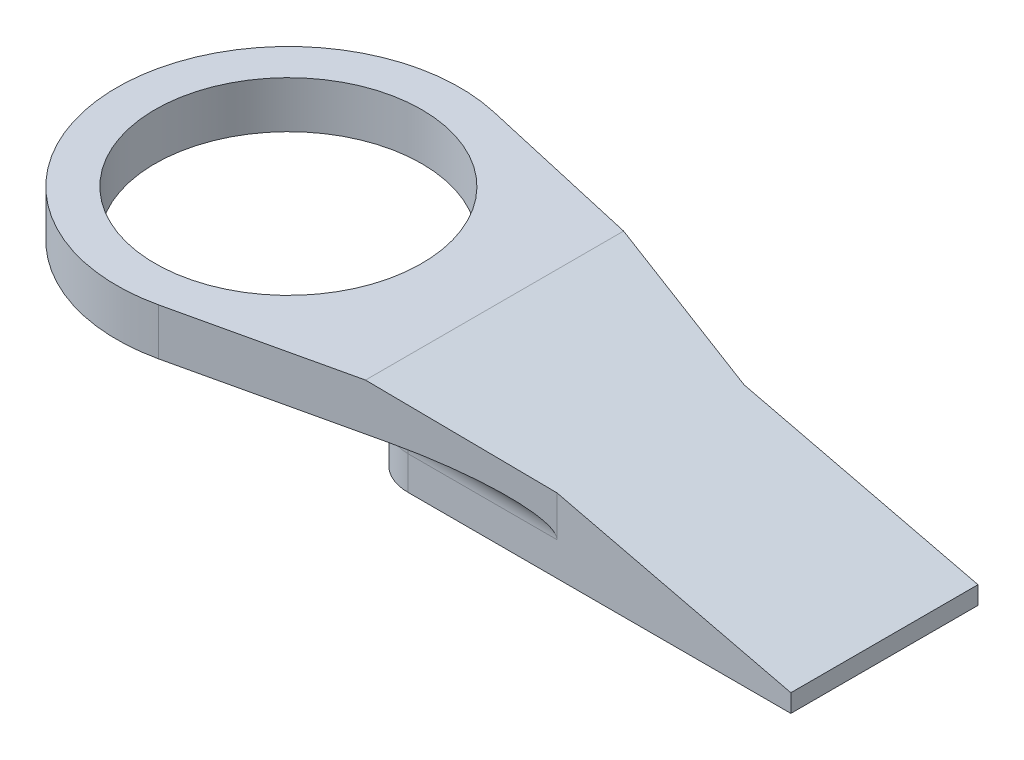
SolidWorks part; units mm, degrees
ref_plane "Front Plane" through (0, 0, 0) normal (0, 0, 1) x (1, 0, 0)
ref_plane "Top Plane" through (0, 0, 0) normal (0, 1, 0) x (1, 0, 0)
ref_plane "Right Plane" through (0, 0, 0) normal (1, 0, 0) x (0, 0, -1)
sketch "Sketch1" plane through (0, 0, 0) normal (0, 0, 1) x (1, 0, 0)
  line L0 (0, 0) -> (0, 7.15)
  line L1 (0, 7.15) -> (30, 7.15)
  line L2 (30, 7.15) -> (30, 0)
  line L3 (30, 0) -> (0, 0)
extrude "Boss-Extrude1" add sketch "Sketch1" along normal blind 12
sketch "Sketch2" plane through (0, 7.15, 0) normal (0, 1, 0) x (1, 0, 0)
  line L0 (0, -6) -> (-8.2201, -6) construction
  line L1 (0, -12) -> (0, 0) construction
  line L3 (30, 0) -> (0, 0) construction
  line L4 (15, -12) -> (-5.8205, -16.7354)
  line L5 (30, -12) -> (0, -12) construction
  line L6 (15, 0) -> (15, -12)
  line L8 (15, 0) -> (-5.7804, 4.7264)
  arc A5 (-5.7804, 4.7264) -> (-5.7405, -16.7172) centre (-8.2201, -6) ccw
  line M4 (30, 0) -> (0, 0)
  line M5 (0, 0) -> (0, -12)
  line M6 (0, -12) -> (30, -12)
extrude "Boss-Extrude2" add sketch "Sketch2" against normal blind 3 contours M6 M5 M4 region at (-7.0838, 7.15, 6)
sketch "Sketch3" plane through (0, 4.15, 0) normal (0, -1, 0) x (1, 0, 0)
  circle A1 centre (-8.2201, 6) radius 11
extrude "Cut-Extrude1" cut sketch "Sketch3" along normal blind 21
fillet "Fillet1" radius 3 2 edges at (0.9994, 2.075, 0) (0.9994, 2.075, 12)
sketch "Sketch4" plane through (0, 4.15, 0) normal (0, -1, 0) x (1, 0, 0)
  circle A1 centre (-8.2201, 6) radius 8.55
extrude "Cut-Extrude2" cut sketch "Sketch4" against normal blind 10
chamfer "Chamfer1" distance 6 distance2 25 1 edges at (30, 7.15, 6) first distance on face at (30, 3.575, 6)
sketch "Sketch5" plane through (0, 0, 0) normal (0, -1, 0) x (-1, 0, 0)
  line L0 (-2.4547, -9) -> (-2.4547, -3)
  line L1 (-2.4547, -3) -> (-3.7108, -3)
  line L2 (-3.7108, -3) -> (-3.7108, -9)
  line L3 (-3.7108, -9) -> (-2.4547, -9)
  arc A0 (-5.4547, -12) -> (-2.5244, -8.3571) centre (-5.4547, -9) ccw construction
  arc A1 (-2.5244, -3.6429) -> (-5.4547, 0) centre (-5.4547, -3) ccw construction
extrude "Boss-Extrude3" add sketch "Sketch5" against normal blind 5
fillet "Fillet2" radius 2 5 edges at (10.2273, 4.15, 0) (10.2273, 4.15, 12) (3.3334, 4.15, 11.1213) (2.4547, 4.15, 6) (3.3334, 4.15, 0.8787)
